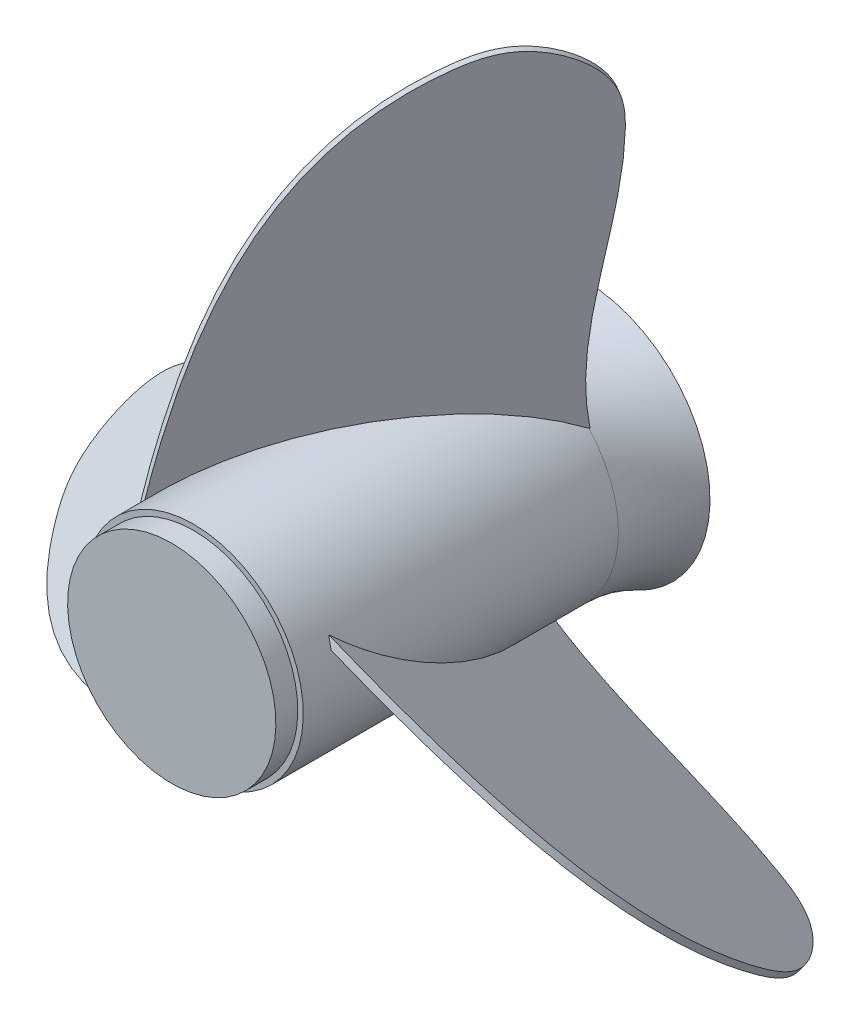
SolidWorks part; units mm, degrees
material "Thornel Mat VMA"
ref_plane "Front Plane" through (0, 0, 0) normal (0, 0, 1) x (1, 0, 0)
ref_plane "Top Plane" through (0, 0, 0) normal (0, 1, 0) x (1, 0, 0)
ref_plane "Right Plane" through (0, 0, 0) normal (1, 0, 0) x (0, 0, -1)
sketch "Sketch1" plane through (0, 0, 0) normal (1, 0, 0) x (0, 0, -1)
  line L0 (75, 46.4183) -> (75, 0)
  line L1 (75, 0) -> (-75, 0)
  line L2 (-75, 0) -> (-75, 38)
  line L3 (-75, 38) -> (-67, 38)
  line L4 (-67, 38) -> (-67, 40)
  line L5 (-67, 40) -> (48, 40)
  arc A0 (48, 40) -> (75, 46.4183) centre (48, 100) ccw
  point P9 (0, 0)
  dimension "D6" = 60
  dimension "D1" = 2
  dimension "D2" = 8
  dimension "D3" = 150
  dimension "D4" = 38
  dimension "D5" = 115
revolve "Revolve1" add sketch "Sketch1" angle 360 about L1
ref_axis "Axis1" through (0, -51.0601, 0) along (0, 1, 0)
ref_plane "Plane1" through (0, 0, 0) normal (-0.866, 0, -0.5) x (0, 1, 0)
sketch "Sketch3" plane through (0, 0, 0) normal (-0.866, 0, -0.5) x (0, 1, 0)
  line L0 (14, 60) -> (14, -65)
  line L1 (150, -13.3423) -> (150, 40.3336) construction
  line L2 (543.6435, -132.7745) -> (-522.4825, 255.2636) construction
  line L3 (491.2083, -31.7855) -> (-281.0437, 175.1388) construction
  line L4 (-626.3735, -189.476) -> (670.2465, 62.5614) construction
  spline S0 degree 1 poles (14, 60) (130, 56.233) knots 0 0 1 1
  spline S1 degree 3 poles (14, 60) (49.2385, 47.1742) (88.0982, 67.1383) (138.8804, 65.6293) (153.1376, 39.5635) (135.608, -24.165) (84.6772, -51.2618) (14, -65) knots 0 0 0 0 0.319631 0.366429 0.456704 0.521189 1 1 1 1
  point P3 (130, 65)
  point P4 (150, 34)
  dimension "D8" = 70
  dimension "D9" = 125
  dimension "D10" = 75
  dimension "D11" = 150
  dimension "D12" = 210
  dimension "D13" = 79
  dimension "D14" = 240
  dimension "D1" = 65
  dimension "D2" = 60
  dimension "D3" = 14
  dimension "D4" = 130
  dimension "D5" = 150
  dimension "D6" = 34
  dimension "D7" = 65
extrude "Boss-Extrude1" add sketch "Sketch3" along normal mid plane 2.5 contours S1 L0
pattern_circular "CirPattern1" count 3 over 360 about axis through (0, 0, 75) along (0, 0, -1) of "Boss-Extrude1"
